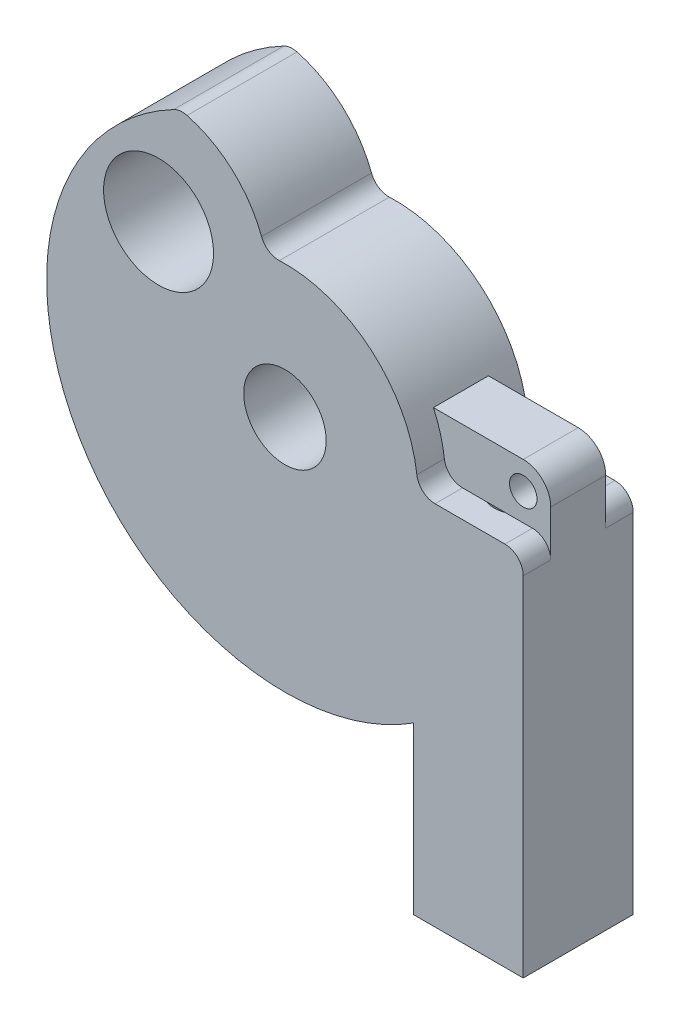
SolidWorks part; units mm, degrees
ref_plane "Front Plane" through (0, 0, 0) normal (0, 0, 1) x (1, 0, 0)
ref_plane "Top Plane" through (0, 0, 0) normal (0, 1, 0) x (1, 0, 0)
ref_plane "Right Plane" through (0, 0, 0) normal (1, 0, 0) x (0, 0, -1)
sketch "Sketch2" plane through (0, 0, 0) normal (0, 0, 1) x (1, 0, 0)
  line L0 (13, 0) -> (13, -20)
  line L1 (13, -20) -> (7, -20)
  line L2 (7, -20) -> (7, -10.9545)
  line L3 (10, 0) -> (10, -20) construction
  arc A0 (13, 0) -> (7, -10.9545) centre (0, 0) ccw
  circle A1 centre (0, 0) radius 10 construction
  dimension "Diameter" = 20
  dimension "Rod Holer Thickness" = 6
  dimension "Rod Holder Length" = 20
extrude "Boss-Extrude1" add sketch "Sketch2" along normal mid plane 6
hole_wizard "M4 Clearance Hole1" positions "Sketch3" profile "Sketch4" hole size "M4" standard "ANSI Metric" end condition up to next
sketch "Sketch3" plane through (0, 0, 3) normal (0, 0, 1) x (1, 0, 0)
  point P2 (0, 0)
sketch "Sketch4" plane through (0, 0, 3) normal (1, 0, 0) x (0, -1, 0)
  line L0 (0, 0) -> (0, 6)
  line L1 (0, 6) -> (2.25, 6)
  line L2 (2.25, 6) -> (2.25, 0)
  line L5 (2.25, 0) -> (0, 0)
  line L11 (0, -6.35) -> (0, 107.95) construction
  dimension "Thru Hole Dia." = 4.5
  dimension "Thru Hole Depth" = 6
sketch "Sketch5" plane through (0, -20, 0) normal (0, -1, 0) x (1, 0, 0)
  line L0 (13, 3) -> (7, -3) construction
  circle A0 centre (10, 0) radius 1.59
  dimension "Rod Hole Diameter" = 3.18
extrude "Cut-Extrude1" cut sketch "Sketch5" against normal blind 20
ref_axis "Axis1" through (10, 0, 0) along (0, -1, 0)
sketch "Sketch8" plane through (0, 0, 3) normal (0, 0, 1) x (1, 0, 0)
  line L0 (0, 0) -> (-21.8723, 0) construction
  line L1 (0, 0) -> (-6.8944, 5.7851) construction
  circle A0 centre (-6.8944, 5.7851) radius 3
  dimension "D2" = 6
  dimension "D1" = 40
  dimension "D3" = 9
extrude "Cut-Extrude3" cut sketch "Sketch8" against normal through all
sketch "Sketch9" plane through (0, 0, 3) normal (0, 0, 1) x (1, 0, 0)
  line L1 (13, 0) -> (7.25, 0)
  line L2 (13, 0) -> (13, 10.075) construction
  arc A0 (13, 0) -> (7, -10.9545) centre (0, 0) ccw construction
  arc A1 (7.25, 0) -> (-1.057, 7.1725) centre (0, 0) ccw
  circle A2 centre (0, 0) radius 2.25 construction
  arc A4 (-1.057, 7.1725) -> (-5.7272, 11.6705) centre (-6.8944, 5.7851) ccw
  circle A5 centre (-6.8944, 5.7851) radius 3 construction
  arc A6 (13, 0) -> (-5.7272, 11.6705) centre (0, 0) ccw
  dimension "D1" = 5
  dimension "D2" = 3
extrude "Cut-Extrude4" cut sketch "Sketch9" against normal through all
sketch "Sketch6" plane through (0, 0, 0) normal (0, 0, 1) x (1, 0, 0)
  line L4 (13, 1.5) -> (13, 0)
  line L6 (11.5, 3) -> (6.6002, 3)
  line L8 (7.25, 0) -> (13, 0) construction
  line L9 (7.25, 0) -> (13, 0)
  arc A2 (13, 1.5) -> (11.5, 3) centre (11.5, 1.5) ccw
  arc A3 (7.25, 0) -> (-1.057, 7.1725) centre (0, 0) ccw construction
  arc A4 (7.25, 0) -> (6.6002, 3) centre (0, 0) ccw
  dimension "Spring Attchment Diameter" = 1.5
extrude "Boss-Extrude2" add sketch "Sketch6" along normal mid plane 3
fillet "Fillet1" radius 1 6 edges at (-5.7272, 11.6705, 0) (7.25, 0, 2.25) (7.25, 0, -2.25) (-1.057, 7.1725, 0) (13, 0, -2.25) (13, 0, 2.25)
sketch "Sketch7" plane through (0, 0, 1.5) normal (0, 0, 1) x (1, 0, 0)
  circle A0 centre (11.5, 1.5) radius 0.75
  arc A1 (13, 1.5) -> (11.5, 3) centre (11.5, 1.5) ccw construction
  dimension "Spring Hole Diam" = 1.5
extrude "Cut-Extrude2" cut sketch "Sketch7" against normal through all both and the other way through all
